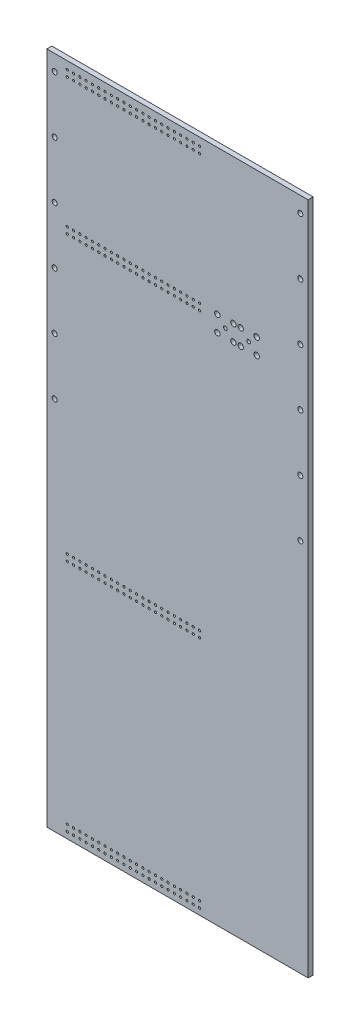
SolidWorks part; units mm, degrees
ref_plane "Front Plane" through (0, 0, 0) normal (0, 0, 1) x (1, 0, 0)
ref_plane "Top Plane" through (0, 0, 0) normal (0, 1, 0) x (1, 0, 0)
ref_plane "Right Plane" through (0, 0, 0) normal (1, 0, 0) x (0, 0, -1)
sketch "Sketch1" plane through (0, 0, 0) normal (0, 0, 1) x (1, 0, 0)
  line L1 (-41.5, -107) -> (41.5, -107)
  line L2 (-41.5, -107) -> (-41.5, 107)
  line L3 (-41.5, 107) -> (41.5, 107)
  line L4 (41.5, -107) -> (41.5, 107)
  line L5 (-41.5, -107) -> (41.5, 107) construction
  line L6 (-41.5, 107) -> (41.5, -107) construction
  point P0 (0, 0)
  dimension "D1" = 83
  dimension "D2" = 214
extrude "Boss-Extrude1" add sketch "Sketch1" along normal blind 1.5875
hole_wizard "#0 Clearance Hole1" positions "Sketch5" profile "Sketch3" hole size "#0" standard "ANSI Inch"
sketch "Sketch5" plane through (0, 0, 1.5875) normal (0, 0, 1) x (1, 0, 0)
  line L0 (0, 0) -> (0, 107) construction
  line L1 (41.5, 107) -> (-41.5, 107) construction
  line L4 (-41.5, 107) -> (-41.5, -107) construction
  line L5 (-41.5, 0) -> (41.5, 0) construction
  line L6 (41.5, -107) -> (41.5, 107) construction
  line L8 (-41.5, 7) -> (41.5, 7) construction
  line L9 (-41.5, 7) -> (-41.5, 107) construction
  line L10 (-41.5, 107) -> (41.5, 107) construction
  line L11 (41.5, 7) -> (41.5, 107) construction
  point P490 (-39, 102)
  point P557 (39, 102)
  point P558 (39, 84)
  point P559 (39, 66)
  point P560 (39, 48)
  point P561 (39, 30)
  point P562 (39, 12)
  point P563 (-39, 84)
  point P564 (-39, 66)
  point P565 (-39, 48)
  point P566 (-39, 30)
  point P567 (-39, 12)
  dimension "D1" = 2.5
  dimension "D2" = 6
  dimension "D4" = 2.5
  dimension "D3" = 2
  dimension "D5" = 100
  dimension "D6" = 5
  dimension "D7" = 5
sketch "Sketch3" plane through (-39, 102, 1.5875) normal (1, 0, 0) x (0, -1, 0)
  line L0 (0, 0) -> (0, 3.6596)
  line L1 (0, 3.6596) -> (0.8064, 3.175)
  line L2 (0.8064, 3.175) -> (0.8064, 0)
  line L5 (0.8064, 0) -> (0, 0)
  line L10 (0, 3.6596) -> (-0.8065, 3.175) construction
  line L11 (0, -6.35) -> (0, 107.95) construction
  dimension "Hole Dia." = 1.6129
  dimension "Hole Depth" = 3.175
  dimension "Drill Angle" = 118
sketch "Sketch6" plane through (0, 0, 0) normal (0, 0, -1) x (-1, 0, 0)
  line L0 (41.5, -7) -> (-41.5, -7) construction
  line L1 (-36.2, 0) -> (36.3, 0)
  line L2 (-36.2, 0) -> (-36.2, -7)
  line L3 (-36.2, -7) -> (36.3, -7)
  line L4 (36.3, 0) -> (36.3, -7)
  dimension "D1" = 72.5
extrude "Boss-Extrude3" add sketch "Sketch6" along normal blind 4.9125
sketch "Sketch7" plane through (0, 0, 1.5875) normal (0, 0, 1) x (1, 0, 0)
  line L0 (0, 107) -> (0, -107) construction
  line L1 (41.5, 107) -> (-41.5, 107) construction
  line L2 (-41.5, -107) -> (41.5, -107) construction
  line L3 (-36, 62.325) -> (8, 62.325) construction
  line L4 (-36, 105.5) -> (8, 105.5) construction
  line L5 (-36, 105.5) -> (-36, 101.5) construction
  line L6 (-36, 101.5) -> (8, 101.5) construction
  line L7 (8, 105.5) -> (8, 101.5) construction
  line L8 (-36, 62.325) -> (-36, 58.325) construction
  line L9 (-36, 58.325) -> (8, 58.325) construction
  line L10 (8, 62.325) -> (8, 58.325) construction
  line L11 (-36, 60.325) -> (41.5, 60.325) construction
  line L12 (41.5, -107) -> (41.5, 107) construction
  line L13 (-36, -27.675) -> (8, -27.675) construction
  line L14 (11.7, 62.065) -> (18.7, 62.065) construction
  line L15 (11.7, 62.065) -> (11.7, 55.065) construction
  line L16 (11.7, 55.065) -> (18.7, 55.065) construction
  line L17 (18.7, 62.065) -> (18.7, 55.065) construction
  line L18 (-36, -27.675) -> (-36, -31.675) construction
  line L19 (-36, -31.675) -> (8, -31.675) construction
  line L20 (8, -27.675) -> (8, -31.675) construction
  line L21 (-36, -102) -> (8, -102) construction
  line L22 (-36, -102) -> (-36, -106) construction
  line L23 (-36, -106) -> (8, -106) construction
  line L24 (8, -102) -> (8, -106) construction
  line L25 (19.1, 62.065) -> (26.1, 62.065) construction
  line L26 (19.1, 62.065) -> (19.1, 55.065) construction
  line L27 (19.1, 55.065) -> (26.1, 55.065) construction
  line L28 (26.1, 62.065) -> (26.1, 55.065) construction
  circle A0 centre (-35, 102.5) radius 0.35
  circle A1 centre (-33, 102.5) radius 0.35
  circle A2 centre (-31, 102.5) radius 0.35
  circle A3 centre (-29, 102.5) radius 0.35
  circle A4 centre (-27, 102.5) radius 0.35
  circle A5 centre (-25, 102.5) radius 0.35
  circle A6 centre (-23, 102.5) radius 0.35
  circle A7 centre (-21, 102.5) radius 0.35
  circle A8 centre (-19, 102.5) radius 0.35
  circle A9 centre (-17, 102.5) radius 0.35
  circle A10 centre (-15, 102.5) radius 0.35
  circle A11 centre (-13, 102.5) radius 0.35
  circle A12 centre (-11, 102.5) radius 0.35
  circle A13 centre (-9, 102.5) radius 0.35
  circle A14 centre (-7, 102.5) radius 0.35
  circle A15 centre (-5, 102.5) radius 0.35
  circle A16 centre (-3, 102.5) radius 0.35
  circle A17 centre (-1, 102.5) radius 0.35
  circle A18 centre (1, 102.5) radius 0.35
  circle A19 centre (3, 102.5) radius 0.35
  circle A20 centre (5, 102.5) radius 0.35
  circle A21 centre (7, 102.5) radius 0.35
  circle A22 centre (-33, 104.5) radius 0.35
  circle A23 centre (-31, 104.5) radius 0.35
  circle A24 centre (-29, 104.5) radius 0.35
  circle A25 centre (-27, 104.5) radius 0.35
  circle A26 centre (-25, 104.5) radius 0.35
  circle A27 centre (-23, 104.5) radius 0.35
  circle A28 centre (-21, 104.5) radius 0.35
  circle A29 centre (-19, 104.5) radius 0.35
  circle A30 centre (-17, 104.5) radius 0.35
  circle A31 centre (-15, 104.5) radius 0.35
  circle A32 centre (-13, 104.5) radius 0.35
  circle A33 centre (-11, 104.5) radius 0.35
  circle A34 centre (-9, 104.5) radius 0.35
  circle A35 centre (-7, 104.5) radius 0.35
  circle A36 centre (-5, 104.5) radius 0.35
  circle A37 centre (-3, 104.5) radius 0.35
  circle A38 centre (-1, 104.5) radius 0.35
  circle A39 centre (1, 104.5) radius 0.35
  circle A40 centre (3, 104.5) radius 0.35
  circle A41 centre (5, 104.5) radius 0.35
  circle A42 centre (7, 104.5) radius 0.35
  circle A43 centre (-35, 104.5) radius 0.35
  circle A44 centre (-35, 59.325) radius 0.35
  circle A45 centre (-33, 59.325) radius 0.35
  circle A46 centre (-31, 59.325) radius 0.35
  circle A47 centre (-29, 59.325) radius 0.35
  circle A48 centre (-27, 59.325) radius 0.35
  circle A49 centre (-25, 59.325) radius 0.35
  circle A50 centre (-23, 59.325) radius 0.35
  circle A51 centre (-21, 59.325) radius 0.35
  circle A52 centre (-19, 59.325) radius 0.35
  circle A53 centre (-17, 59.325) radius 0.35
  circle A54 centre (-15, 59.325) radius 0.35
  circle A55 centre (-13, 59.325) radius 0.35
  circle A56 centre (-11, 59.325) radius 0.35
  circle A57 centre (-9, 59.325) radius 0.35
  circle A58 centre (-7, 59.325) radius 0.35
  circle A59 centre (-5, 59.325) radius 0.35
  circle A60 centre (-3, 59.325) radius 0.35
  circle A61 centre (-1, 59.325) radius 0.35
  circle A62 centre (1, 59.325) radius 0.35
  circle A63 centre (3, 59.325) radius 0.35
  circle A64 centre (5, 59.325) radius 0.35
  circle A65 centre (7, 59.325) radius 0.35
  circle A66 centre (-33, 61.325) radius 0.35
  circle A67 centre (-31, 61.325) radius 0.35
  circle A68 centre (-29, 61.325) radius 0.35
  circle A69 centre (-27, 61.325) radius 0.35
  circle A70 centre (-25, 61.325) radius 0.35
  circle A71 centre (-23, 61.325) radius 0.35
  circle A72 centre (-21, 61.325) radius 0.35
  circle A73 centre (-19, 61.325) radius 0.35
  circle A74 centre (-17, 61.325) radius 0.35
  circle A75 centre (-15, 61.325) radius 0.35
  circle A76 centre (-13, 61.325) radius 0.35
  circle A77 centre (-11, 61.325) radius 0.35
  circle A78 centre (-9, 61.325) radius 0.35
  circle A79 centre (-7, 61.325) radius 0.35
  circle A80 centre (-5, 61.325) radius 0.35
  circle A81 centre (-3, 61.325) radius 0.35
  circle A82 centre (-1, 61.325) radius 0.35
  circle A83 centre (1, 61.325) radius 0.35
  circle A84 centre (3, 61.325) radius 0.35
  circle A85 centre (5, 61.325) radius 0.35
  circle A86 centre (7, 61.325) radius 0.35
  circle A87 centre (-35, 61.325) radius 0.35
  circle A88 centre (15.2, 58.565) radius 0.5842
  circle A89 centre (12.66, 61.105) radius 0.8509
  circle A90 centre (17.74, 61.105) radius 0.8509
  circle A91 centre (17.74, 56.025) radius 0.8509
  circle A92 centre (12.66, 56.025) radius 0.8509
  circle A93 centre (15.2, 58.565) radius 0.24 construction
  circle A94 centre (-35, -30.675) radius 0.35
  circle A95 centre (-33, -30.675) radius 0.35
  circle A96 centre (-31, -30.675) radius 0.35
  circle A97 centre (-29, -30.675) radius 0.35
  circle A98 centre (-27, -30.675) radius 0.35
  circle A99 centre (-25, -30.675) radius 0.35
  circle A100 centre (-23, -30.675) radius 0.35
  circle A101 centre (-21, -30.675) radius 0.35
  circle A102 centre (-19, -30.675) radius 0.35
  circle A103 centre (-17, -30.675) radius 0.35
  circle A104 centre (-15, -30.675) radius 0.35
  circle A105 centre (-13, -30.675) radius 0.35
  circle A106 centre (-11, -30.675) radius 0.35
  circle A107 centre (-9, -30.675) radius 0.35
  circle A108 centre (-7, -30.675) radius 0.35
  circle A109 centre (-5, -30.675) radius 0.35
  circle A110 centre (-3, -30.675) radius 0.35
  circle A111 centre (-1, -30.675) radius 0.35
  circle A112 centre (1, -30.675) radius 0.35
  circle A113 centre (3, -30.675) radius 0.35
  circle A114 centre (5, -30.675) radius 0.35
  circle A115 centre (7, -30.675) radius 0.35
  circle A116 centre (-33, -28.675) radius 0.35
  circle A117 centre (-31, -28.675) radius 0.35
  circle A118 centre (-29, -28.675) radius 0.35
  circle A119 centre (-27, -28.675) radius 0.35
  circle A120 centre (-25, -28.675) radius 0.35
  circle A121 centre (-23, -28.675) radius 0.35
  circle A122 centre (-21, -28.675) radius 0.35
  circle A123 centre (-19, -28.675) radius 0.35
  circle A124 centre (-17, -28.675) radius 0.35
  circle A125 centre (-15, -28.675) radius 0.35
  circle A126 centre (-13, -28.675) radius 0.35
  circle A127 centre (-11, -28.675) radius 0.35
  circle A128 centre (-9, -28.675) radius 0.35
  circle A129 centre (-7, -28.675) radius 0.35
  circle A130 centre (-5, -28.675) radius 0.35
  circle A131 centre (-3, -28.675) radius 0.35
  circle A132 centre (-1, -28.675) radius 0.35
  circle A133 centre (1, -28.675) radius 0.35
  circle A134 centre (3, -28.675) radius 0.35
  circle A135 centre (5, -28.675) radius 0.35
  circle A136 centre (7, -28.675) radius 0.35
  circle A137 centre (-35, -28.675) radius 0.35
  circle A138 centre (-35, -105) radius 0.35
  circle A139 centre (-33, -105) radius 0.35
  circle A140 centre (-31, -105) radius 0.35
  circle A141 centre (-29, -105) radius 0.35
  circle A142 centre (-27, -105) radius 0.35
  circle A143 centre (-25, -105) radius 0.35
  circle A144 centre (-23, -105) radius 0.35
  circle A145 centre (-21, -105) radius 0.35
  circle A146 centre (-19, -105) radius 0.35
  circle A147 centre (-17, -105) radius 0.35
  circle A148 centre (-15, -105) radius 0.35
  circle A149 centre (-13, -105) radius 0.35
  circle A150 centre (-11, -105) radius 0.35
  circle A151 centre (-9, -105) radius 0.35
  circle A152 centre (-7, -105) radius 0.35
  circle A153 centre (-5, -105) radius 0.35
  circle A154 centre (-3, -105) radius 0.35
  circle A155 centre (-1, -105) radius 0.35
  circle A156 centre (1, -105) radius 0.35
  circle A157 centre (3, -105) radius 0.35
  circle A158 centre (5, -105) radius 0.35
  circle A159 centre (7, -105) radius 0.35
  circle A160 centre (-33, -103) radius 0.35
  circle A161 centre (-31, -103) radius 0.35
  circle A162 centre (-29, -103) radius 0.35
  circle A163 centre (-27, -103) radius 0.35
  circle A164 centre (-25, -103) radius 0.35
  circle A165 centre (-23, -103) radius 0.35
  circle A166 centre (-21, -103) radius 0.35
  circle A167 centre (-19, -103) radius 0.35
  circle A168 centre (-17, -103) radius 0.35
  circle A169 centre (-15, -103) radius 0.35
  circle A170 centre (-13, -103) radius 0.35
  circle A171 centre (-11, -103) radius 0.35
  circle A172 centre (-9, -103) radius 0.35
  circle A173 centre (-7, -103) radius 0.35
  circle A174 centre (-5, -103) radius 0.35
  circle A175 centre (-3, -103) radius 0.35
  circle A176 centre (-1, -103) radius 0.35
  circle A177 centre (1, -103) radius 0.35
  circle A178 centre (3, -103) radius 0.35
  circle A179 centre (5, -103) radius 0.35
  circle A180 centre (7, -103) radius 0.35
  circle A181 centre (-35, -103) radius 0.35
  circle A182 centre (22.6, 58.565) radius 0.5842
  circle A183 centre (20.06, 61.105) radius 0.8509
  circle A184 centre (25.14, 61.105) radius 0.8509
  circle A185 centre (25.14, 56.025) radius 0.8509
  circle A186 centre (20.06, 56.025) radius 0.8509
  circle A187 centre (22.6, 58.565) radius 0.24 construction
  dimension "D1" = 0.7
  dimension "D14" = 1.1684
  dimension "D15" = 1.7018
  dimension "D27" = 0.48
  dimension "D4" = 2
  dimension "D5" = 42
  dimension "D6" = 1
  dimension "D7" = 1
  dimension "D8" = 4
  dimension "D9" = 44
  dimension "D10" = 15
  dimension "D11" = 2.5
  dimension "D12" = 2
  dimension "D13" = 7.2
  dimension "D16" = 2.54
  dimension "D17" = 2.54
  dimension "D20" = 5.08
  dimension "D21" = 5.08
  dimension "D22" = 7
  dimension "D23" = 3.5
  dimension "D24" = 3.5
  dimension "D25" = 48.675
  dimension "D26" = 2
  dimension "D29" = 7.4
  dimension "D30" = 90
  dimension "D32" = 1
  dimension "D2" = 22
  dimension "D3" = 2
  dimension "D18" = 2
  dimension "D19" = 2
  dimension "D28" = 2
  dimension "D31" = 2
extrude "Cut-Extrude1" cut sketch "Sketch7" against normal through all
